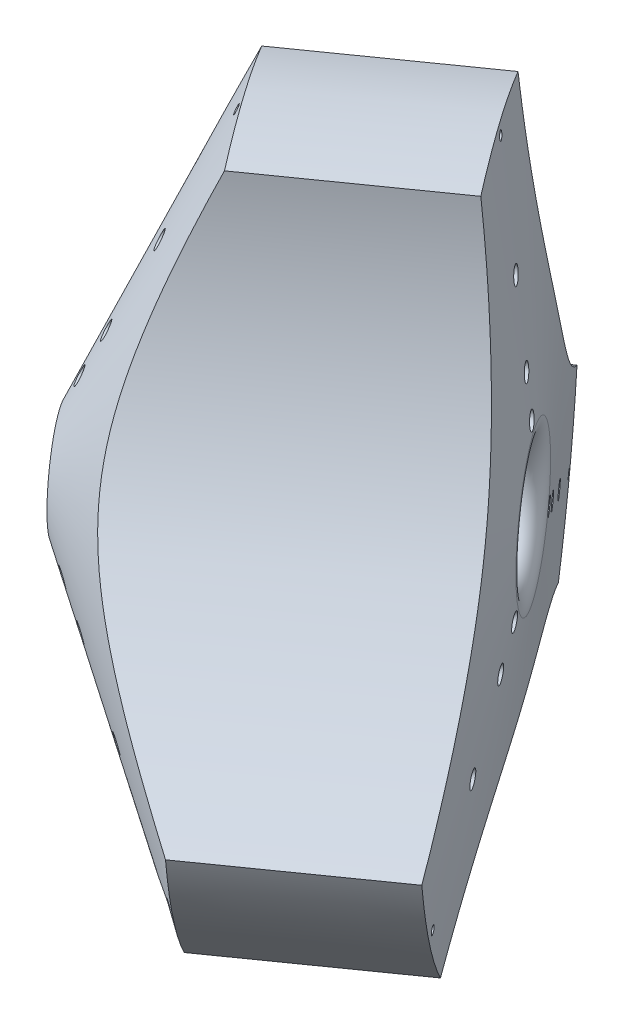
SolidWorks part; units mm, degrees
material "ABS"
ref_plane "前视基准面" through (0, 0, 0) normal (0, 0, 1) x (1, 0, 0)
ref_plane "上视基准面" through (0, 0, 0) normal (0, 1, 0) x (1, 0, 0)
ref_plane "右视基准面" through (0, 0, 0) normal (1, 0, 0) x (0, 0, -1)
other "Configuration Table"
sketch "草图1" plane through (0, 0, 0) normal (0, 1, 0) x (1, 0, 0)
  line L0 (0, 0) -> (50000, 0) construction
  line L1 (0, 0) -> (43301.2702, 25000) construction
  line L2 (0, 0) -> (25000.0005, 43301.2699) construction
  line L3 (0, 0) -> (0, 50000) construction
  line L4 (0, 0) -> (-24999.9998, 43301.2703) construction
  line L5 (0, 0) -> (-43301.2699, 25000.0005) construction
  line L10 (-81.0426, 140.3699) -> (-40.226, 69.6734)
  line L11 (-40.226, 69.6734) -> (-76.4152, 44.1183)
  line L12 (-76.4152, 44.1183) -> (-153.9525, 88.8845)
  line L13 (18.3541, 0) -> (55.6014, 0)
  line L14 (-293.1662, 0) -> (-96.7748, 0)
  line L15 (-153.9525, 88.8845) -> (-81.0426, 140.3699)
  line L16 (-112.7056, 118.0111) -> (-106.9373, 109.8424) construction
  line L17 (-106.9373, 109.8424) -> (-76.0217, 131.6735)
  line L18 (-106.9373, 109.8424) -> (-144.4146, 83.3778)
  spline S0 degree 4 poles (0, -13.9122) (0.4288, -13.9878) (1.2926, -14.1039) (2.6002, -14.1722) (4.3419, -14.0551) (6.0103, -13.7444) (7.773, -13.21) (9.593, -12.4079) (11.2813, -11.3833) (13.0108, -9.9981) (14.579, -8.3636) (15.8921, -6.573) (16.7894, -4.9125) (17.3145, -3.6768) (17.5885, -2.9241) (17.7037, -2.5872) (17.8123, -2.2481) (17.9142, -1.9072) (18.0095, -1.5637) (18.0983, -1.2182) (18.1691, -0.9197) (18.2269, -0.6559) (18.2831, -0.3813) (18.3354, -0.109) (18.3711, 0.0925) (18.4139, 0.3573) (18.4465, 0.5746) (18.4705, 0.7447) (18.4976, 0.9523) (18.5267, 1.1986) (18.5568, 1.4891) (18.5855, 1.8227) (18.6082, 2.1561) (18.625, 2.4897) (18.6415, 2.9908) (18.6444, 3.7428) (18.6, 4.7901) (18.4544, 6.1268) (18.1183, 7.9493) (17.5241, 9.9881) (16.6153, 12.1533) (15.4328, 14.2054) (14.026, 16.1623) (12.2754, 18.1012) (10.149, 19.9482) (7.4457, 21.6944) (4.4784, 23.0742) (1.2971, 24.0486) (-2.1866, 24.6091) (-5.9175, 24.6633) (-9.7618, 24.1432) (-13.6227, 23.0043) (-17.2722, 21.3076) (-20.6387, 19.103) (-24.4169, 15.784) (-28.1648, 11.0227) (-31.3154, 4.4225) (-32.9538, -4.4321) (-32.0375, -14.0948) (-28.1424, -23.7302) (-21.3685, -32.1908) (-12.5515, -38.4704) (-2.4126, -42.2287) (8.3331, -43.3372) (19.0234, -41.8455) (29.7828, -37.6697) (40.3424, -30.2375) (49.4452, -19.1893) (55.5551, -4.7492) (57.3753, 11.4017) (54.7581, 27.4228) (48.0949, 42.2071) (37.9905, 54.8719) (25.1812, 64.7711) (10.4646, 71.4886) (-5.3559, 74.8179) (-21.5135, 74.7355) (-37.3086, 71.3698) (-52.1281, 64.9701) (-65.4574, 55.8769) (-76.8843, 44.4931) (-86.0992, 31.2617) (-92.9569, 16.4959) (-98.2612, -3.1071) (-99.3529, -27.5578) (-93.1302, -55.5464) (-77.0987, -83.8533) (-53.8578, -106.5556) (-25.4602, -122.2617) (5.9606, -130.2467) (38.3519, -130.3634) (69.8553, -122.9377) (98.8778, -108.6588) (124.1284, -88.4759) (144.6286, -63.5047) (159.7045, -34.9474) (168.9656, -4.026) (172.2746, 28.0696) (169.7138, 60.222) (161.5485, 91.4149) (148.1919, 120.752) (130.171, 147.4681) (108.095, 170.9338) (82.6276, 190.6548) (54.4619, 206.2675) (24.299, 217.5313) (-7.1689, 224.319) (-39.2739, 226.6058) (-71.3835, 224.4579) (-98.969, 218.8252) (-121.9134, 211.4493) (-140.4165, 203.6877) (-154.7919, 196.546) (-168.6874, 188.5108) (-182.0538, 179.6235) (-196.4446, 168.7156) (-208.5171, 158.129) (-219.9251, 146.8372) (-231.9749, 133.3951) (-241.9655, 120.8263) (-251.0758, 107.6061) (-258.3626, 95.6046) (-263.2354, 86.8412) (-266.9323, 79.7223) (-270.4259, 72.5015) (-273.7143, 65.185) (-276.4108, 58.7049) (-278.5921, 53.0984) (-280.3227, 48.3937) (-281.6549, 44.6108) (-282.9345, 40.8105) (-284.1616, 36.9917) (-285.3356, 33.1583) (-286.4574, 29.3057) (-287.5253, 25.4437) (-288.5419, 21.5581) (-289.5026, 17.675) (-290.3013, 14.2402) (-290.9454, 11.3302) (-291.4717, 8.8337) (-291.8579, 6.9561) (-292.2757, 4.8213) (-292.5987, 3.1456) (-293.0036, 0.9209) (-293.2168, -0.28) (-293.5445, -2.179) (-293.8363, -3.9367) (-294.1828, -6.1075) (-294.5484, -8.5333) (-294.8987, -10.9902) (-295.2261, -13.4346) (-295.5347, -15.89) (-295.8945, -18.9572) (-296.2863, -22.6451) (-296.6843, -26.9519) (-297.0589, -31.8818) (-297.3529, -36.8165) (-297.5669, -41.7558) (-297.7007, -46.6976) (-297.7547, -51.6411) (-297.729, -56.5848) (-297.624, -61.5274) (-297.4397, -66.4677) (-296.9135, -76.3411) (-295.6855, -89.8862) (-293.2164, -107.0261) (-288.82, -127.5848) (-284.8275, -141.8776) (-281.7816, -151.2859) (-280.1641, -155.9573) knots 0 0 0 0 0 0.000986 0.001973 0.002959 0.003945 0.004822 0.006138 0.007453 0.008403 0.009829 0.011255 0.012465 0.012667 0.012868 0.01307 0.013272 0.013473 0.013675 0.013876 0.014078 0.014179 0.01428 0.014481 0.01467 0.014765 0.01486 0.014954 0.015049 0.015238 0.015427 0.015617 0.015806 0.015995 0.016184 0.016752 0.017509 0.018368 0.019228 0.020946 0.022309 0.023673 0.024581 0.026398 0.028215 0.030031 0.031848 0.033788 0.035728 0.037999 0.04027 0.042541 0.044813 0.047084 0.049355 0.053897 0.05844 0.063467 0.069524 0.07558 0.081637 0.087693 0.093749 0.099806 0.105862 0.111919 0.119671 0.128756 0.137841 0.146925 0.15601 0.165095 0.174179 0.183264 0.192349 0.201434 0.210519 0.219603 0.228688 0.237773 0.246858 0.255942 0.265027 0.274475 0.292645 0.310814 0.328984 0.347153 0.365322 0.383492 0.401661 0.41983 0.438 0.456169 0.474339 0.492508 0.510678 0.528847 0.547017 0.565186 0.583356 0.601525 0.619695 0.637864 0.656034 0.674203 0.692373 0.710542 0.728712 0.746881 0.755966 0.765051 0.774136 0.78322 0.792305 0.80139 0.815017 0.81956 0.828644 0.842271 0.851356 0.855899 0.860441 0.864984 0.869526 0.874068 0.878611 0.880882 0.883153 0.885424 0.887695 0.889967 0.892238 0.894509 0.89678 0.899052 0.901323 0.903594 0.90473 0.905865 0.907001 0.908137 0.909272 0.910408 0.911108 0.911808 0.913208 0.914607 0.916007 0.917407 0.918807 0.920207 0.921607 0.924407 0.927206 0.930006 0.932806 0.935606 0.938405 0.941205 0.944005 0.946805 0.949604 0.952404 0.966403 0.977602 0.988801 1 1 1 1 1 construction
  spline S1 degree 4 poles (18.3541, 0) (18.3671, 0.0737) (18.3859, 0.1846) (18.4139, 0.3573) (18.4465, 0.5746) (18.4705, 0.7447) (18.4976, 0.9523) (18.5267, 1.1986) (18.5568, 1.4891) (18.5855, 1.8227) (18.6082, 2.1561) (18.625, 2.4897) (18.6415, 2.9908) (18.6444, 3.7428) (18.6, 4.7901) (18.4544, 6.1268) (18.1183, 7.9493) (17.5241, 9.9881) (16.6153, 12.1533) (15.4328, 14.2054) (14.026, 16.1623) (12.2754, 18.1012) (10.149, 19.9482) (7.4457, 21.6944) (4.4784, 23.0742) (1.2971, 24.0486) (-2.1866, 24.6091) (-5.9175, 24.6633) (-9.7618, 24.1432) (-13.6227, 23.0043) (-17.2722, 21.3076) (-20.6387, 19.103) (-24.4169, 15.784) (-28.1648, 11.0227) (-31.3154, 4.4225) (-32.9538, -4.4321) (-32.0375, -14.0948) (-28.1424, -23.7302) (-21.3685, -32.1908) (-12.5515, -38.4704) (-2.4126, -42.2287) (8.3331, -43.3372) (19.0234, -41.8455) (29.7828, -37.6697) (40.3424, -30.2375) (49.4452, -19.1893) (55.5551, -4.7492) (57.3753, 11.4017) (54.7581, 27.4228) (48.0949, 42.2071) (37.9905, 54.8719) (25.1812, 64.7711) (10.4646, 71.4886) (-5.3559, 74.8179) (-21.5135, 74.7355) (-37.3086, 71.3698) (-52.1281, 64.9701) (-65.4574, 55.8769) (-76.8843, 44.4931) (-86.0992, 31.2617) (-92.9569, 16.4959) (-98.2612, -3.1071) (-99.3529, -27.5578) (-93.1302, -55.5464) (-77.0987, -83.8533) (-53.8578, -106.5556) (-25.4602, -122.2617) (5.9606, -130.2467) (38.3519, -130.3634) (69.8553, -122.9377) (98.8778, -108.6588) (124.1284, -88.4759) (144.6286, -63.5047) (159.7045, -34.9474) (168.9656, -4.026) (172.2746, 28.0696) (169.7138, 60.222) (161.5485, 91.4149) (148.1919, 120.752) (130.171, 147.4681) (108.095, 170.9338) (82.6276, 190.6548) (54.4619, 206.2675) (24.299, 217.5313) (-7.1689, 224.319) (-39.2739, 226.6058) (-71.3835, 224.4579) (-98.969, 218.8252) (-121.9134, 211.4493) (-140.4165, 203.6877) (-154.7919, 196.546) (-168.6874, 188.5108) (-182.0538, 179.6235) (-196.4446, 168.7156) (-208.5171, 158.129) (-219.9251, 146.8372) (-231.9749, 133.3951) (-241.9655, 120.8263) (-251.0758, 107.6061) (-258.3626, 95.6046) (-263.2354, 86.8412) (-266.9323, 79.7223) (-270.4259, 72.5015) (-273.7143, 65.185) (-276.4108, 58.7049) (-278.5921, 53.0984) (-280.3227, 48.3937) (-281.6549, 44.6108) (-282.9345, 40.8105) (-284.1616, 36.9917) (-285.3356, 33.1583) (-286.4574, 29.3057) (-287.5253, 25.4437) (-288.5419, 21.5581) (-289.5026, 17.675) (-290.3013, 14.2402) (-290.9454, 11.3302) (-291.4717, 8.8337) (-291.8579, 6.9561) (-292.2757, 4.8213) (-292.5987, 3.1456) (-292.9346, 1.3001) (-293.0882, 0.4423) (-293.1662, 0) knots 0.014481 0.014481 0.014481 0.014481 0.014481 0.01467 0.014765 0.01486 0.014954 0.015049 0.015238 0.015427 0.015617 0.015806 0.015995 0.016184 0.016752 0.017509 0.018368 0.019228 0.020946 0.022309 0.023673 0.024581 0.026398 0.028215 0.030031 0.031848 0.033788 0.035728 0.037999 0.04027 0.042541 0.044813 0.047084 0.049355 0.053897 0.05844 0.063467 0.069524 0.07558 0.081637 0.087693 0.093749 0.099806 0.105862 0.111919 0.119671 0.128756 0.137841 0.146925 0.15601 0.165095 0.174179 0.183264 0.192349 0.201434 0.210519 0.219603 0.228688 0.237773 0.246858 0.255942 0.265027 0.274475 0.292645 0.310814 0.328984 0.347153 0.365322 0.383492 0.401661 0.41983 0.438 0.456169 0.474339 0.492508 0.510678 0.528847 0.547017 0.565186 0.583356 0.601525 0.619695 0.637864 0.656034 0.674203 0.692373 0.710542 0.728712 0.746881 0.755966 0.765051 0.774136 0.78322 0.792305 0.80139 0.815017 0.81956 0.828644 0.842271 0.851356 0.855899 0.860441 0.864984 0.869526 0.874068 0.878611 0.880882 0.883153 0.885424 0.887695 0.889967 0.892238 0.894509 0.89678 0.899052 0.901323 0.903594 0.90473 0.905865 0.907001 0.908137 0.909272 0.910408 0.910408 0.910408 0.910408 0.910408
  spline S2 degree 4 poles (18.4059, -25.3335) (19.107, -24.9917) (20.4868, -24.262) (22.5206, -23.0115) (25.0808, -21.0705) (27.4721, -18.8597) (29.6657, -16.3937) (31.6129, -13.729) (33.0895, -11.2475) (34.1864, -9.0304) (34.9057, -7.3212) (35.3416, -6.1645) (35.6757, -5.1903) (35.9253, -4.405) (36.1573, -3.6144) (36.3716, -2.8185) (36.5434, -2.119) (36.6687, -1.5643) (36.7535, -1.1663) (36.8052, -0.9135) (36.8466, -0.7052) (36.8982, -0.4372) (36.9567, -0.1214) (37.0035, 0.1434) (37.0749, 0.5721) (37.1371, 0.9717) (37.2058, 1.4486) (37.2819, 2.0322) (37.3587, 2.7131) (37.4304, 3.4924) (37.4863, 4.2735) (37.526, 5.0553) (37.5559, 6.0336) (37.5599, 7.208) (37.5185, 8.5778) (37.4086, 10.1401) (37.1505, 12.4751) (36.6019, 15.5617) (35.6708, 18.9675) (34.2579, 22.6243) (32.7042, 25.7897) (31.1185, 28.4933) (29.3394, 31.0737) (27.3788, 33.5189) (25.249, 35.8182) (22.9627, 37.9617) (20.5329, 39.9412) (17.3329, 42.201) (13.6843, 44.3112) (9.5794, 46.1791) (4.9351, 47.7364) (0.5493, 48.7741) (-5.1759, 49.5807) (-12.2448, 49.6897) (-20.4322, 48.5637) (-29.4144, 45.6531) (-37.7662, 41.2547) (-45.2725, 35.5359) (-51.7593, 28.6855) (-57.0931, 20.9063) (-61.1793, 12.4073) (-63.9591, 3.398) (-65.4072, -5.9169) (-65.5277, -15.3413) (-64.3508, -24.6913) (-61.9292, -33.7971) (-58.3342, -42.5053) (-53.6526, -50.6795) (-47.9834, -58.201) (-41.4348, -64.9693) (-34.1214, -70.9013) (-26.1617, -75.9314) (-17.6761, -80.0102) (-8.7848, -83.1042) (0.3937, -85.1942) (9.7443, -86.2746) (19.1561, -86.3521) (28.5237, -85.4444) (37.7479, -83.5791) (48.7429, -80.1706) (61.3712, -74.3882) (74.9241, -65.3639) (88.2878, -52.3646) (99.2288, -36.9666) (107.3051, -19.8977) (112.3659, -1.711) (114.3597, 17.056) (113.3221, 35.8954) (109.3632, 54.3391) (102.6547, 71.9655) (93.418, 88.4046) (81.9129, 103.34) (68.427, 116.5097) (53.2659, 127.7056) (36.7454, 136.7708) (19.1839, 143.5977) (0.8963, 148.1237) (-17.8115, 150.3284) (-36.6464, 150.2287) (-55.332, 147.8751) (-73.6111, 143.3474) (-91.2474, 136.7503) (-108.0274, 128.21) (-121.7938, 119.1626) (-132.8352, 110.3812) (-141.486, 102.4316) (-148.0599, 95.7143) (-154.2723, 88.6613) (-160.1094, 81.2949) (-165.5592, 73.6375) (-171.8736, 63.7306) (-176.9453, 54.4461) (-180.9636, 45.947) (-183.8818, 38.8929) (-185.1615, 35.6104) (-186.1831, 32.858) (-186.9734, 30.6462) (-187.7366, 28.425) (-188.4727, 26.1945) (-189.1816, 23.9554) (-189.8633, 21.7077) (-190.5178, 19.4522) (-191.145, 17.1886) (-191.7448, 14.9181) (-192.3174, 12.6396) (-192.8623, 10.3561) (-193.3803, 8.0634) (-193.8088, 6.0566) (-194.131, 4.4692) (-194.3554, 3.3245) (-194.4957, 2.592) (-194.6042, 2.0172) (-194.7054, 1.4732) (-194.8177, 0.857) (-194.937, 0.1911) (-195.0219, -0.2913) (-195.1581, -1.0772) (-195.2723, -1.7539) (-195.4156, -2.6211) (-195.5862, -3.6835) (-195.7746, -4.9054) (-195.982, -6.3152) (-196.2274, -8.0725) (-196.5025, -10.1875) (-196.7939, -12.6566) (-197.0869, -15.4841) (-197.3398, -18.3147) (-197.5528, -21.1491) (-197.7258, -23.9859) (-197.8589, -26.8251) (-197.9522, -29.6657) (-198.0191, -33.2178) (-198.0202, -37.4813) (-197.8411, -45.2961) (-197.0568, -56.6437) (-195.3598, -69.3345) (-193.0445, -80.4735) (-191.2905, -87.36) (-190.5403, -90.1013) knots 0 0 0 0 0 0.00302 0.006041 0.00923 0.01242 0.01561 0.0188 0.02199 0.023585 0.02518 0.025978 0.026776 0.027573 0.028371 0.029168 0.029966 0.030365 0.030564 0.030763 0.030963 0.031162 0.031561 0.03194 0.032319 0.032698 0.033077 0.033835 0.034592 0.03535 0.036108 0.036866 0.037624 0.039139 0.040655 0.042171 0.043686 0.048233 0.05278 0.055812 0.058843 0.061874 0.064906 0.067937 0.070969 0.074 0.077031 0.080063 0.086126 0.090292 0.094458 0.099005 0.103552 0.112646 0.12174 0.130835 0.139929 0.149023 0.158117 0.167211 0.176305 0.185399 0.194493 0.203588 0.212682 0.221776 0.23087 0.239964 0.249059 0.258153 0.267247 0.276341 0.285435 0.294529 0.303624 0.312718 0.321812 0.330906 0.34 0.349094 0.36631 0.384498 0.402687 0.420875 0.439063 0.457252 0.47544 0.493628 0.511817 0.530005 0.548193 0.566382 0.58457 0.602758 0.620947 0.639135 0.657323 0.675512 0.6937 0.711888 0.730077 0.748265 0.766453 0.784642 0.793736 0.80283 0.811924 0.821018 0.830112 0.839207 0.848301 0.866489 0.871036 0.875583 0.877857 0.88013 0.882404 0.884678 0.886951 0.889225 0.891498 0.893772 0.896045 0.898319 0.900592 0.902866 0.90514 0.907413 0.90855 0.909118 0.909687 0.910255 0.910823 0.911392 0.91196 0.912648 0.913336 0.914024 0.914711 0.916087 0.917463 0.918838 0.920214 0.922965 0.925716 0.928468 0.931219 0.93397 0.936721 0.939473 0.942224 0.944975 0.950478 0.95598 0.972488 0.988995 1 1 1 1 1 construction
  spline S3 degree 4 poles (36.9778, 0) (36.9927, 0.0848) (37.022, 0.2547) (37.0749, 0.5721) (37.1371, 0.9717) (37.2058, 1.4486) (37.2819, 2.0322) (37.3587, 2.7131) (37.4304, 3.4924) (37.4863, 4.2735) (37.526, 5.0553) (37.5559, 6.0336) (37.5599, 7.208) (37.5185, 8.5778) (37.4086, 10.1401) (37.1505, 12.4751) (36.6019, 15.5617) (35.6708, 18.9675) (34.2579, 22.6243) (32.7042, 25.7897) (31.1185, 28.4933) (29.3394, 31.0737) (27.3788, 33.5189) (25.249, 35.8182) (22.9627, 37.9617) (20.5329, 39.9412) (17.3329, 42.201) (13.6843, 44.3112) (9.5794, 46.1791) (4.9351, 47.7364) (0.5493, 48.7741) (-5.1759, 49.5807) (-12.2448, 49.6897) (-20.4322, 48.5637) (-29.4144, 45.6531) (-37.7662, 41.2547) (-45.2725, 35.5359) (-51.7593, 28.6855) (-57.0931, 20.9063) (-61.1793, 12.4073) (-63.9591, 3.398) (-65.4072, -5.9169) (-65.5277, -15.3413) (-64.3508, -24.6913) (-61.9292, -33.7971) (-58.3342, -42.5053) (-53.6526, -50.6795) (-47.9834, -58.201) (-41.4348, -64.9693) (-34.1214, -70.9013) (-26.1617, -75.9314) (-17.6761, -80.0102) (-8.7848, -83.1042) (0.3937, -85.1942) (9.7443, -86.2746) (19.1561, -86.3521) (28.5237, -85.4444) (37.7479, -83.5791) (48.7429, -80.1706) (61.3712, -74.3882) (74.9241, -65.3639) (88.2878, -52.3646) (99.2288, -36.9666) (107.3051, -19.8977) (112.3659, -1.711) (114.3597, 17.056) (113.3221, 35.8954) (109.3632, 54.3391) (102.6547, 71.9655) (93.418, 88.4046) (81.9129, 103.34) (68.427, 116.5097) (53.2659, 127.7056) (36.7454, 136.7708) (19.1839, 143.5977) (0.8963, 148.1237) (-17.8115, 150.3284) (-36.6464, 150.2287) (-55.332, 147.8751) (-73.6111, 143.3474) (-91.2474, 136.7503) (-108.0274, 128.21) (-121.7938, 119.1626) (-132.8352, 110.3812) (-141.486, 102.4316) (-148.0599, 95.7143) (-154.2723, 88.6613) (-160.1094, 81.2949) (-165.5592, 73.6375) (-171.8736, 63.7306) (-176.9453, 54.4461) (-180.9636, 45.947) (-183.8818, 38.8929) (-185.1615, 35.6104) (-186.1831, 32.858) (-186.9734, 30.6462) (-187.7366, 28.425) (-188.4727, 26.1945) (-189.1816, 23.9554) (-189.8633, 21.7077) (-190.5178, 19.4522) (-191.145, 17.1886) (-191.7448, 14.9181) (-192.3174, 12.6396) (-192.8623, 10.3561) (-193.3803, 8.0634) (-193.8088, 6.0566) (-194.131, 4.4692) (-194.3554, 3.3245) (-194.4957, 2.592) (-194.6042, 2.0172) (-194.7054, 1.4732) (-194.8177, 0.857) (-194.9027, 0.3825) (-194.948, 0.1273) (-194.9705, 0) knots 0.031561 0.031561 0.031561 0.031561 0.031561 0.03194 0.032319 0.032698 0.033077 0.033835 0.034592 0.03535 0.036108 0.036866 0.037624 0.039139 0.040655 0.042171 0.043686 0.048233 0.05278 0.055812 0.058843 0.061874 0.064906 0.067937 0.070969 0.074 0.077031 0.080063 0.086126 0.090292 0.094458 0.099005 0.103552 0.112646 0.12174 0.130835 0.139929 0.149023 0.158117 0.167211 0.176305 0.185399 0.194493 0.203588 0.212682 0.221776 0.23087 0.239964 0.249059 0.258153 0.267247 0.276341 0.285435 0.294529 0.303624 0.312718 0.321812 0.330906 0.34 0.349094 0.36631 0.384498 0.402687 0.420875 0.439063 0.457252 0.47544 0.493628 0.511817 0.530005 0.548193 0.566382 0.58457 0.602758 0.620947 0.639135 0.657323 0.675512 0.6937 0.711888 0.730077 0.748265 0.766453 0.784642 0.793736 0.80283 0.811924 0.821018 0.830112 0.839207 0.848301 0.866489 0.871036 0.875583 0.877857 0.88013 0.882404 0.884678 0.886951 0.889225 0.891498 0.893772 0.896045 0.898319 0.900592 0.902866 0.90514 0.907413 0.90855 0.909118 0.909687 0.910255 0.910823 0.911392 0.91196 0.91196 0.91196 0.91196 0.91196
  dimension "D1" = 10
revolve "旋转1" add sketch "草图1" angle 360 about L15 region at (-87.4731, 0, -85.3286) region at (-58.9371, 0, -57.8903)
ref_plane "基准面1" through (11.3166, 0, -7.9913) normal (0.8169, 0, -0.5768) x (-0.5768, 0, -0.8169)
sketch "草图2" plane through (11.3166, 0, -7.9913) normal (0.8169, 0, -0.5768) x (-0.5768, 0, -0.8169)
  line L0 (161.411, 0) -> (161.411, 20) construction
  line L1 (161.411, 20) -> (161.411, 30) construction
  line L2 (161.411, 30) -> (161.411, 50)
  line L3 (161.411, 0) -> (20.2489, 81.5) construction
  line L4 (161.411, 81.2937) -> (161.411, 78.7937) construction
  circle A0 centre (161.411, 0) radius 81.2937 construction
  circle A1 centre (161.411, 20) radius 2
  circle A2 centre (161.411, 30) radius 2
  circle A3 centre (161.411, 50) radius 2
  circle A4 centre (161.411, 78.7937) radius 1
  circle A5 centre (20.2489, 81.5) radius 122.5
  circle A6 centre (302.5731, 81.5) radius 122.5
  circle A7 centre (229.6483, -39.3969) radius 1
  circle A8 centre (187.3918, -15) radius 2
  circle A9 centre (178.7315, -10) radius 2
  circle A10 centre (161.411, -163) radius 122.5
  circle A11 centre (93.1736, -39.3969) radius 1
  circle A12 centre (135.4302, -15) radius 2
  circle A13 centre (144.0905, -10) radius 2
  circle A14 centre (204.7123, -25) radius 2
  circle A15 centre (118.1097, -25) radius 2
  circle A16 centre (161.411, 0) radius 12.5
  dimension "D7" = 4
  dimension "D8" = 4
  dimension "D9" = 4
  dimension "D10" = 2
  dimension "D11" = 245
  dimension "D14" = 25
  dimension "D1" = 20
  dimension "D2" = 10
  dimension "D3" = 20
  dimension "D4" = 163
  dimension "D5" = 60
  dimension "D6" = 2.5
  dimension "D12" = 3
  dimension "D13" = 3
extrude "切除-拉伸1" cut sketch "草图2" against normal blind 97 contours A5 | A6 | A10 | A16 | A4 | A3 | A2 | A1 | A13 | A12 | A15 | A11 | A9 | A8 | A14 | A7 region at (-0.3635, 81.5, -24.5318) region at (-163.2166, 81.5, -255.1525) region at (-81.79, -163, -139.8421) region at (-81.79, 0, -139.8421)
fillet "圆角1" radius 4.5 1 edges at (-74.7665, 0, -129.4994)
shell "抽壳1" thickness 2
ref_plane "基准面2" through (-91.953, 0, -130.2172) normal (-0.5768, 0, -0.8169) x (-0.8169, 0, 0.5768)
ref_plane "基准面3" through (-93.1067, 0, -131.8509) normal (-0.5768, 0, -0.8169) x (-0.8169, 0, 0.5768)
sketch "草图4" plane through (-93.1067, 0, -131.8509) normal (-0.5768, 0, -0.8169) x (-0.8169, 0, 0.5768)
  line L0 (-11.7252, 16.521) -> (65.2133, 16.521)
  line L1 (-11.0381, 23.792) -> (61.5785, 23.792)
  line L2 (-11.0381, 23.792) -> (-11.0381, 26.214)
  line L3 (-11.0381, 26.214) -> (61.5785, 26.214)
  line L4 (61.5785, 23.792) -> (61.5785, 26.214)
  line L5 (65.2133, 16.521) -> (66.5986, 13.8704)
  line L6 (66.5986, 13.8704) -> (-10.9367, 13.8704)
  line L7 (-10.9367, 13.8704) -> (-11.7252, 15.3792)
  line L8 (-11.7252, 15.3792) -> (-11.7252, 16.521)
  line L9 (-8.5396, 53.4569) -> (47.8256, 53.4569)
  line L10 (47.8256, 53.4569) -> (38.1161, 76.5488)
  line L11 (38.1161, 76.5488) -> (-6.6658, 76.5488)
  line L12 (-6.6658, 76.5488) -> (-8.5396, 53.4569)
  spline S0 degree 3 poles (-7.3305, 79.1172) (-7.7888, 73.9475) (-8.2331, 68.8328) (-9.0768, 58.7085) (-9.4767, 53.6989) (-10.0105, 46.2622) (-10.1772, 43.7963) (-10.4027, 40.117) (-10.4736, 38.8962) (-10.6049, 36.4786) (-10.6654, 35.2799) (-10.9389, 29.336) (-11.0622, 24.7396) (-11.0639, 15.8583) (-10.9423, 11.5734) (-10.669, 6.4179) (-10.6084, 5.3961) (-10.4769, 3.3764) (-10.4062, 2.3824) (-10.182, -0.5528) (-10.0162, -2.4473) (-9.484, -7.9487) (-9.0842, -11.3741) (-8.4498, -16.1515) (-8.2322, -17.6836) (-7.7877, -20.6254) (-7.5602, -22.0373) (-7.3305, -23.3766) knots 0 0 0 0 0.125 0.125 0.25 0.25 0.3125 0.3125 0.34375 0.34375 0.375 0.375 0.5 0.5 0.625 0.625 0.65625 0.65625 0.6875 0.6875 0.75 0.75 0.875 0.875 0.9375 0.9375 1 1 1 1 construction
  spline S1 degree 3 poles (36.9721, -23.3766) (39.1895, -20.8131) (41.352, -18.0051) (44.4603, -13.4138) (45.4734, -11.8198) (47.4349, -8.4969) (48.3836, -6.768) (50.1864, -3.1615) (51.0408, -1.2839) (52.2154, 1.6619) (52.589, 2.6665) (53.285, 4.7016) (53.6082, 5.7344) (54.4919, 8.8806) (54.9661, 11.0417) (55.6177, 15.504) (55.7941, 17.8053) (55.7989, 21.3726) (55.7574, 22.5685) (55.5928, 24.9646) (55.4697, 26.1663) (54.989, 29.7832) (54.5196, 32.2099) (53.6424, 35.8779) (53.3213, 37.1052) (52.6293, 39.5702) (52.2578, 40.8105) (51.0862, 44.5271) (50.2326, 46.9936) (48.4292, 51.92) (47.4791, 54.3798) (45.5129, 59.3032) (44.4966, 61.7666) (42.4162, 66.7033) (41.3521, 69.1767) (39.7283, 72.8973) (39.1825, 74.1392) (38.0825, 76.627) (37.5283, 77.8729) (36.9721, 79.1172) knots 0 0 0 0 0.125 0.125 0.1875 0.1875 0.25 0.25 0.3125 0.3125 0.34375 0.34375 0.375 0.375 0.4375 0.4375 0.5 0.5 0.53125 0.53125 0.5625 0.5625 0.625 0.625 0.65625 0.65625 0.6875 0.6875 0.75 0.75 0.8125 0.8125 0.875 0.875 0.9375 0.9375 0.96875 0.96875 1 1 1 1 construction
extrude "凸台-拉伸1" add sketch "草图4" along normal mid plane 1
ref_axis "基准轴1" through (-128.4976, 0, -106.8595) along (0.8169, 0, -0.5768)
pattern_circular "阵列(圆周)1" count 3 over 360 about axis through (-128.4976, 0, -106.8595) along (0.8169, 0, -0.5768) of "凸台-拉伸1"
